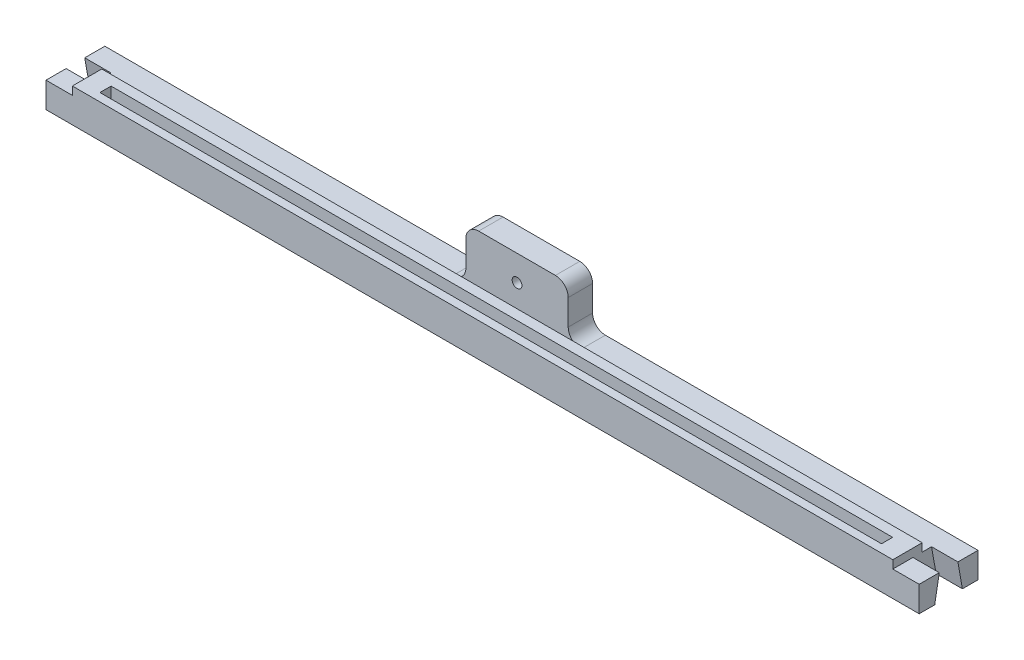
SolidWorks part; units mm, degrees
note: The reader was unsure of these and kept them because the rebuilt part matched: shared geometry of "Sketch2<3>".
ref_plane "Front Plane" through (0, 0, 0) normal (0, 0, 1) x (1, 0, 0)
ref_plane "Top Plane" through (0, 0, 0) normal (0, 1, 0) x (1, 0, 0)
ref_plane "Right Plane" through (0, 0, 0) normal (1, 0, 0) x (0, 0, -1)
sketch "Sketch1" plane through (0, 0, 0) normal (0, 1, 0) x (1, 0, 0)
  line L0 (-320.75, 23) -> (-320.75, 7.291)
  line L1 (-341.35, 23) -> (341.35, 23)
  line L2 (-341.35, 23) -> (-341.35, -23)
  line L3 (-341.35, -23) -> (341.35, -23)
  line L4 (341.35, 23) -> (341.35, -23)
  line L5 (-341.35, 23) -> (341.35, -23) construction
  line L6 (-341.35, -23) -> (341.35, 23) construction
  line L7 (320.75, 23) -> (320.75, -23)
  line L8 (-320.75, -7.291) -> (-320.75, -23)
  line L9 (-320.75, 7.291) -> (-320.75, -7.291)
  line L10 (-320.75, 7.291) -> (-341.35, 7.291)
  line L11 (-320.75, -7.291) -> (-341.35, -7.291)
  line L12 (0, 23) -> (0, -23) construction
  line L13 (320.75, -7.291) -> (341.35, -7.291)
  line L14 (320.75, 7.291) -> (341.35, 7.291)
  point P0 (0, 0)
  dimension "D1" = 20.6
  dimension "D2" = 20.6
  dimension "D3" = 46
  dimension "D4" = 641.5
  dimension "D5" = 15.709
  dimension "D6" = 14.582
extrude "Boss-Extrude1" add sketch "Sketch1" along normal blind 20 contours L2 L3 L0 L1 | L7 L1 L0 L3 | L8 L11 L2 L3 | L13 L7 L3 L4 | L7 L14 L4 L1
sketch "Sketch2" plane through (0, 20, 0) normal (0, 1, 0) x (1, 0, 0)
  line L0 (-305.55, 0) -> (305.55, 0)
  line L1 (-341.35, -23) -> (341.35, -23)
  line L2 (-341.35, -23) -> (-341.35, -7.9188)
  line L3 (-341.35, -7.9188) -> (341.35, -7.9188)
  line L4 (341.35, -23) -> (341.35, -7.9188)
  line L5 (341.35, 23) -> (341.35, 7.291) construction
  line L6 (-341.35, -23) -> (341.35, -23)
  line L7 (-341.35, -23) -> (-341.35, -16.65)
  line L8 (-341.35, -16.65) -> (341.35, -16.65)
  line L9 (341.35, -23) -> (341.35, -16.65)
  line L10 (-341.35, -7.9188) -> (341.35, -7.9188)
  line L11 (-341.35, -7.9188) -> (-341.35, -1.5688)
  line L12 (-341.35, -1.5688) -> (341.35, -1.5688)
  line L13 (341.35, -7.9188) -> (341.35, -1.5688)
  line L14 (305.55, 23) -> (305.55, -23)
  line L15 (-341.35, 23) -> (341.35, 23) construction
  line L16 (-305.55, 23) -> (-305.55, -23)
  line L17 (0, 23) -> (0, -23) construction
  line L18 (-305.55, -23) -> (-320.75, -23)
  line L19 (-305.55, -23) -> (-305.55, 0)
  line L20 (-305.55, 0) -> (-320.75, 0)
  line L21 (-320.75, -23) -> (-320.75, 0)
  line L22 (305.55, 0) -> (320.75, 0)
  line L23 (320.75, -23) -> (320.75, 0)
  point P15 (0, 0)
  line M5 (-341.35, -23) -> (341.35, -23)
  line M6 (341.35, -23) -> (341.35, -7.291)
  dimension "D1" = 15.0812
  dimension "D2" = 6.35
  dimension "D3" = 21.4312
  dimension "D4" = 611.1
  dimension "D5" = 641.5
extrude "Boss-Extrude2" add sketch "Sketch2" along normal blind 6.35 contours L8 L2 M5 M6 | L12 L16 L0 L14 | L12 L17 L3 L14 | L8 L17 L14 M5 | L12 L23 L22 L14 | L10 L23 L12 L14 | L8 L23 L10 L14 | L6 L23 L8 L14 | L21 L12 L16 L20 | L21 L10 L16 L12 | L21 L8 L16 L10 | L21 L6 L16 L8 | L17 L12 L16 L10 | L0 L17 L12 L14
sketch "Sketch4" plane through (0, 20, 0) normal (0, 1, 0) x (1, 0, 0)
  line L0 (-341.35, 23) -> (341.35, 23) construction
  line L1 (-40, 3.95) -> (40, 3.95)
  line L2 (-40, 3.95) -> (-40, 42.05)
  line L3 (-40, 42.05) -> (40, 42.05)
  line L4 (40, 3.95) -> (40, 42.05)
  line L5 (-40, 3.95) -> (40, 42.05) construction
  line L6 (-40, 42.05) -> (40, 3.95) construction
  line L7 (-40, 23) -> (40, 23)
  point P0 (0, 23)
  line M11 (341.35, 23) -> (-341.35, 23)
  dimension "D1" = 80
  dimension "D2" = 38.1
extrude "Boss-Extrude3" add sketch "Sketch4" along normal blind 40 contours L1 L4 L2 M11
sketch "Sketch5" plane through (0, 0, -23) normal (0, 0, -1) x (-1, 0, 0)
  line L0 (-40, 60) -> (40, 20)
  line L1 (-40, 20) -> (40, 20)
  line L2 (-40, 20) -> (-40, 60)
  line L3 (-40, 60) -> (40, 60)
  line L4 (40, 20) -> (40, 60)
  line L5 (40, 60) -> (-40, 20)
  circle A0 centre (0, 40) radius 3.81
  dimension "D1" = 7.62
extrude "Cut-Extrude2" cut sketch "Sketch5" against normal blind 50.8 contours L5 A0 L0 | L0 A0 L5 | L5 A0 L0 | L0 A0 L5
chamfer "Chamfer1" distance 20 angle 10 4 edges at (331.05, 0, -7.291) (331.05, 0, 7.291) (-331.05, 0, 7.291) (-331.05, 0, -7.291)
extrude "Cut-Extrude3" cut sketch "Sketch2<3>" against normal blind 20 contours L17 L10 L16 L8 | L3 L17 L8 L14
sketch "Sketch2<3>" plane through (0, 20, 0) normal (0, 1, 0) x (1, 0, 0) same geometry as "Sketch2"
fillet "Fillet1" radius 10 4 edges at (-40, 20, -13.475) (-40, 60, -13.475) (40, 60, -13.475) (40, 20, -13.475)
